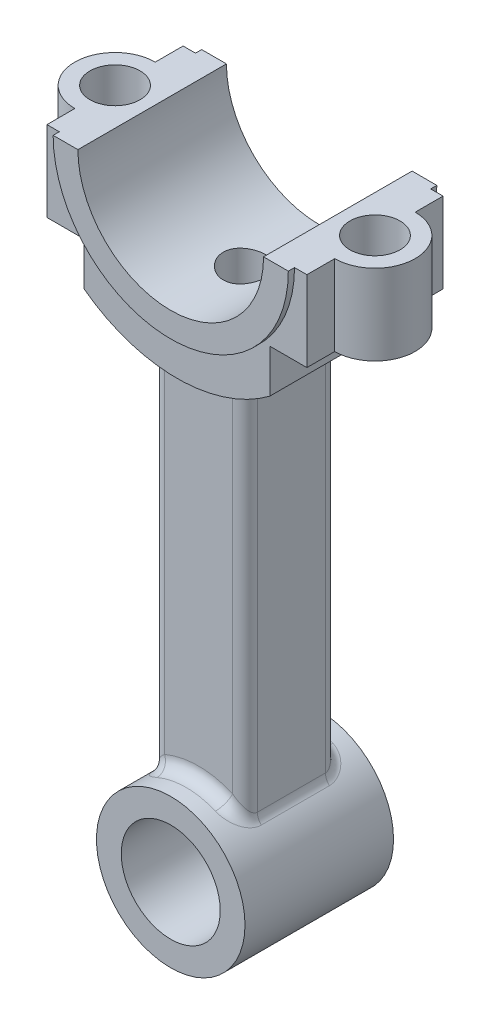
SolidWorks part; units mm, degrees
material "Сталь"
ref_plane "Спереди" through (0, 0, 0) normal (0, 0, 1) x (1, 0, 0)
ref_plane "Сверху" through (0, 0, 0) normal (0, 1, 0) x (1, 0, 0)
ref_plane "Справа" through (0, 0, 0) normal (1, 0, 0) x (0, 0, -1)
sketch "Эскиз1" plane through (0, 0, 0) normal (0, 0, 1) x (1, 0, 0)
  circle A0 centre (0, 0) radius 12
  circle A1 centre (0, 0) radius 8
  dimension "D1" = 24
  dimension "D2" = 16
extrude "Бобышка-Вытянуть1" add sketch "Эскиз1" along normal blind 12 and the other way blind 12
sketch "Эскиз3" plane through (0, 0, 0) normal (0, 0, 1) x (1, 0, 0)
  line L0 (-27.5, 95) -> (27.5, 95)
  line L1 (-27.5, 82) -> (27.5, 82)
  line L2 (-27.5, 82) -> (-27.5, 108)
  line L3 (-27.5, 108) -> (27.5, 108)
  line L4 (27.5, 82) -> (27.5, 108)
  line L5 (-27.5, 82) -> (27.5, 108) construction
  line L6 (-27.5, 108) -> (27.5, 82) construction
  line L8 (-15, 70) -> (15, 70)
  line L9 (-15, 70) -> (-15, 82)
  line L10 (-15, 82) -> (15, 82)
  line L11 (15, 70) -> (15, 82)
  line L12 (-15, 70) -> (15, 82) construction
  line L13 (-15, 82) -> (15, 70) construction
  circle A0 centre (0, 95) radius 15
  circle A1 centre (0, 95) radius 25
  point P10 (0, 76)
  dimension "D1" = 30
  dimension "D3" = 50
  dimension "D2" = 95
  dimension "D4" = 55
  dimension "D5" = 26
  dimension "D6" = 30
extrude "Бобышка-Вытянуть2" add sketch "Эскиз3" along normal blind 11 and the other way blind 11 separate body contours L9 A1 L11 L1 A0 | L0 A1 L1 A0 | A1 L0 L2 L1 | L1 A1 L0 A0 | A1 L1 L4 L0 region at (18.1695, 88.1711, 0) region at (25.5044, 87.4436, 0) region at (-18.1695, 88.1711, 0) region at (0, 76.3817, 0) region at (-25.5044, 87.4436, 0)
sketch "Эскиз2" plane through (0, 0, 0) normal (0, 1, 0) x (1, 0, 0)
  line L1 (-7.5, -7.5) -> (7.5, -7.5)
  line L2 (-7.5, -7.5) -> (-7.5, 7.5)
  line L3 (-7.5, 7.5) -> (7.5, 7.5)
  line L4 (7.5, -7.5) -> (7.5, 7.5)
  line L5 (-7.5, -7.5) -> (7.5, 7.5) construction
  line L6 (-7.5, 7.5) -> (7.5, -7.5) construction
  point P0 (0, 0)
  dimension "D1" = 15
extrude "Бобышка-Вытянуть3" add sketch "Эскиз2" along normal up to surface and the other way up to surface from offset 30 up to face at (0, 72.5, 0) other way up to face at (12, 0, -12)
sketch "Эскиз4" plane through (0, 82, 0) normal (0, -1, 0) x (1, 0, 0)
  circle A0 centre (21, 0) radius 4.05
  dimension "D1" = 8.1
  dimension "D2" = 21
extrude "Вырез-Вытянуть1" cut sketch "Эскиз4" against normal through all
mirror "Зеркальное отражение1" about plane through (0, 0, 0) normal (1, 0, 0) of "Вырез-Вытянуть1"
fillet "Скругление1" radius 2 12 edges at (0, 12, 7.5) (0, 12, -7.5) (0, 70, -7.5) (0, 70, 7.5) (7.5, 9.3675, 0) (7.5, 40.2595, 7.5) (7.5, 71.1515, 0) (7.5, 40.2595, -7.5) (-7.5, 9.3675, 0) (-7.5, 40.2595, -7.5) (-7.5, 71.1515, 0) (-7.5, 40.2595, 7.5)
sketch "Эскиз5" plane through (0, 0, 11) normal (0, 0, 1) x (1, 0, 0)
  line L0 (15, 95) -> (27.5, 95) construction
  line L1 (-27.5, 95) -> (-15, 95) construction
  line L2 (-19, 95) -> (-15, 95)
  line L3 (15, 95) -> (19, 95)
  arc A0 (-15, 95) -> (15, 95) centre (0, 95) ccw construction
  arc A1 (-15, 95) -> (15, 95) centre (0, 95) ccw
  arc A2 (19, 95) -> (-19, 95) centre (0, 95) cw
  dimension "D1" = 19
extrude "Бобышка-Вытянуть4" add sketch "Эскиз5" along normal blind 1
mirror "Зеркальное отражение2" about plane through (0, 0, 0) normal (0, 0, 1) of "Бобышка-Вытянуть4"
sketch "Эскиз6" plane through (0, 0, 0) normal (0, 1, 0) x (1, 0, 0)
  circle A0 centre (0, 0) radius 3.5
  dimension "D1" = 7
extrude "Вырез-Вытянуть2" cut sketch "Эскиз6" along normal through all
sketch "Эскиз7" plane through (0, 82, 0) normal (0, -1, 0) x (1, 0, 0)
  line L0 (27.5, -11) -> (27.5, 11) construction
  line L1 (21, 6.5) -> (21, 11)
  line L2 (15, 11) -> (27.5, 11) construction
  line L3 (21, 11) -> (27.5, 11)
  line L4 (27.5, 11) -> (27.5, -11)
  line L5 (27.5, -11) -> (21, -11)
  line L6 (15, -11) -> (27.5, -11) construction
  line L7 (21, -11) -> (21, -6.5)
  circle A0 centre (21, 0) radius 6.5
  line M2 (27.5, 11) -> (15, 11)
  line M4 (15, -11) -> (27.5, -11)
  line M5 (27.5, -11) -> (27.5, 11)
extrude "Вырез-Вытянуть3" cut sketch "Эскиз7" against normal through all contours A0 L7 M4 M5 | A0 L4 L1 M2 region at (24.6755, 82, 7.874) region at (24.6755, 82, -7.874)
mirror "Зеркальное отражение3" about plane through (0, 0, 0) normal (1, 0, 0) of "Вырез-Вытянуть3"
equation "\"0ю5\"=1"
